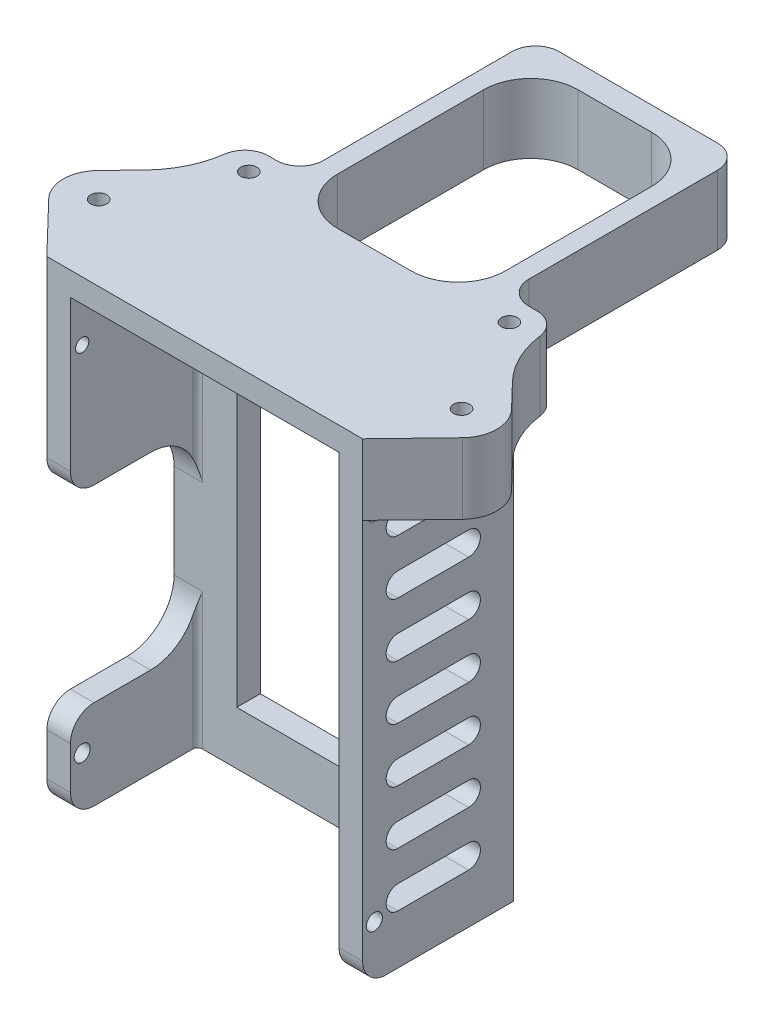
SolidWorks part; units mm, degrees
ref_plane "前视基准面" through (0, 0, 0) normal (0, 0, 1) x (1, 0, 0)
ref_plane "上视基准面" through (0, 0, 0) normal (0, 1, 0) x (1, 0, 0)
ref_plane "右视基准面" through (0, 0, 0) normal (1, 0, 0) x (0, 0, -1)
sketch "草图1" plane through (0, 0, 0) normal (0, 0, 1) x (1, 0, 0)
  line L1 (33.5, -59) -> (-33.5, -59)
  line L2 (33.5, -59) -> (33.5, 59)
  line L3 (33.5, 59) -> (-33.5, 59)
  line L4 (-33.5, -59) -> (-33.5, 59)
  line L5 (33.5, -59) -> (-33.5, 59) construction
  line L6 (33.5, 59) -> (-33.5, -59) construction
  point P0 (0, 0)
  dimension "D1" = 67
  dimension "D2" = 118
extrude "凸台-拉伸1" add sketch "草图1" along normal blind 32
shell "抽壳2" thickness 5
sketch "草图2" plane through (0, 0, 0) normal (0, 0, -1) x (-1, 0, 0)
  line L1 (20.2, -30.7) -> (-21.8, -30.7)
  line L2 (20.2, -30.7) -> (20.2, 44.3)
  line L3 (20.2, 44.3) -> (-21.8, 44.3)
  line L4 (-21.8, -30.7) -> (-21.8, 44.3)
  line L5 (-33.5, 59) -> (33.5, 59) construction
  line L6 (-33.5, -59) -> (-33.5, 59) construction
  point P0 (0, 0)
  dimension "D1" = 42
  dimension "D2" = 75
  dimension "D3" = 14.7
  dimension "D4" = 11.7
extrude "切除-拉伸1" cut sketch "草图2" against normal blind 5
sketch "草图3" plane through (0, 0, 0) normal (0, 0, -1) x (-1, 0, 0)
  line L0 (-21.8, -30.7) -> (20.2, -30.7) construction
  line L1 (-21.8, 44.3) -> (-21.8, -30.7) construction
  line L2 (20.2, 44.3) -> (-21.8, 44.3) construction
  line L3 (20.2, -30.7) -> (20.2, 44.3) construction
  line L4 (-21.8, -30.7) -> (20.2, -30.7)
  line L5 (-21.8, 44.3) -> (-21.8, -30.7)
  line L6 (20.2, 44.3) -> (-21.8, 44.3)
  line L7 (20.2, -30.7) -> (20.2, 44.3)
  line L8 (-25.8, -34.7) -> (24.2, -34.7)
  line L9 (24.2, -34.7) -> (24.2, 48.3)
  line L10 (24.2, 48.3) -> (-25.8, 48.3)
  line L11 (-25.8, 48.3) -> (-25.8, -34.7)
  dimension "D1" = 4
extrude "凸台-拉伸2" [suppressed] add sketch "草图3" along normal blind 24
sketch "草图4" plane through (-33.5, 0, 0) normal (-1, 0, 0) x (0, 0, 1)
  line L0 (32, 17) -> (1, 17)
  line L1 (32, 59) -> (32, -59) construction
  line L2 (1, -23) -> (1, 17)
  line L3 (1, -23) -> (32, -23)
  line L4 (32, -23) -> (32, 17)
  line L5 (32, 59) -> (0, 59) construction
  dimension "D1" = 42
  dimension "D2" = 40
  dimension "D3" = 31
extrude "切除-拉伸2" cut sketch "草图4" against normal blind 5
sketch "草图5" [suppressed] plane through (0, 0, -24) normal (0, 0, -1) x (-1, 0, 0)
  line L0 (0, 72.1156) -> (0, -68.0472) construction
  line L1 (-24.25, 45.3) -> (-14.25, 45.3)
  line L2 (-24.25, 45.3) -> (-24.25, 52.05)
  line L3 (14.25, 45.3) -> (14.25, 52.05)
  line L4 (-14.25, 45.3) -> (-14.25, 52.05)
  line L5 (-35.1719, 4.55) -> (42.7838, 4.55) construction
  line L6 (24.25, 45.3) -> (24.25, 52.05)
  line L7 (24.25, 45.3) -> (14.25, 45.3)
  line L8 (-14.25, -36.2) -> (-14.25, -42.95)
  line L9 (-24.25, -36.2) -> (-24.25, -42.95)
  line L10 (-24.25, -36.2) -> (-14.25, -36.2)
  line L11 (24.25, -36.2) -> (14.25, -36.2)
  line L12 (24.25, -36.2) -> (24.25, -42.95)
  line L13 (14.25, -36.2) -> (14.25, -42.95)
  arc A0 (-24.25, 52.05) -> (-14.25, 52.05) centre (-19.25, 52.05) cw
  circle A1 centre (-19.25, 52.05) radius 2.15
  circle A2 centre (19.25, 52.05) radius 2.15
  arc A3 (24.25, 52.05) -> (14.25, 52.05) centre (19.25, 52.05) ccw
  circle A4 centre (-19.25, -42.95) radius 2.15
  arc A5 (-24.25, -42.95) -> (-14.25, -42.95) centre (-19.25, -42.95) ccw
  arc A6 (24.25, -42.95) -> (14.25, -42.95) centre (19.25, -42.95) cw
  circle A7 centre (19.25, -42.95) radius 2.15
  dimension "D2" = 5
  dimension "D3" = 4.3
  dimension "D1" = 6.75
extrude "凸台-拉伸3" [suppressed] add sketch "草图5" against normal blind 8
ref_plane "基准面1" [suppressed] through (0, 0, -16) normal (0, 0, 1) x (1, 0, 0)
fillet "圆角2" [suppressed] radius 11
sketch "草图6" [suppressed] plane through (0, 0, -16) normal (0, 0, 1) x (1, 0, 0)
  line L0 (0, 85.8102) -> (0, -80.0918) construction
  line L1 (45.1986, 4.55) -> (-38.9545, 4.55) construction
  circle A0 centre (-19.25, -42.95) radius 3.75
  circle A1 centre (-19.25, 52.05) radius 3.75
  circle A2 centre (19.25, 52.05) radius 3.75
  circle A3 centre (19.25, -42.95) radius 3.75
  dimension "D1" = 7.5
extrude "切除-拉伸3" [suppressed] cut sketch "草图6" along normal blind 8
fillet "圆角3" [suppressed] radius 11
sketch "草图7" plane through (-33.5, 0, 0) normal (-1, 0, 0) x (0, 0, 1)
  line L0 (32, 59) -> (0, 59) construction
  line L1 (32, 59) -> (32, 17) construction
  line L3 (32, -23) -> (32, -59) construction
  circle A0 centre (29.5, 44) radius 1.4
  circle A2 centre (29.5, -31) radius 1.7
  dimension "D1" = 15
  dimension "D2" = 2.5
  dimension "D3" = 2.8
  dimension "D4" = 75
  dimension "D5" = 2.5
  dimension "D6" = 3.4
extrude "切除-拉伸4" cut sketch "草图7" against normal through all
sketch "草图9" plane through (-33.5, 0, 0) normal (-1, 0, 0) x (0, 0, 1)
  line L0 (0, 59) -> (0, -59) construction
  line L1 (32, -59) -> (0, -59)
  line L2 (32, -59) -> (32, -42)
  line L3 (32, -42) -> (0, -42)
  line L4 (0, -59) -> (0, -42)
  dimension "D1" = 17
extrude "切除-拉伸6" cut sketch "草图9" against normal through all
sketch "草图10" plane through (0, 0, 5) normal (0, 0, 1) x (1, 0, 0)
  line L0 (21.8, -30.7) -> (-20.2, -30.7) construction
  line L1 (-44.2, 59) -> (45.8, 59)
  line L2 (-44.2, 59) -> (-44.2, -42)
  line L3 (-44.2, -42) -> (45.8, -42)
  line L4 (45.8, 59) -> (45.8, -42)
  line L5 (21.8, 44.3) -> (21.8, -30.7) construction
  line L6 (-20.2, -30.7) -> (-20.2, 44.3) construction
  line L7 (-20.2, 44.3) -> (21.8, 44.3) construction
  line L8 (21.8, -30.7) -> (-20.2, -30.7)
  line L9 (21.8, 44.3) -> (21.8, -30.7)
  line L10 (-20.2, -30.7) -> (-20.2, 44.3)
  line L11 (-20.2, 44.3) -> (21.8, 44.3)
  line L12 (33.5, 59) -> (-33.5, 59) construction
  line L13 (28.5, -42) -> (-28.5, -42) construction
  line L14 (21.8, 6.8) -> (-20.2, 6.8) construction
  line L15 (0.8, 44.3) -> (0.8, -30.7) construction
  circle A0 centre (39.8, 39.3) radius 1.7
  circle A1 centre (39.8, -25.7) radius 1.7
  circle A2 centre (-38.2, -25.7) radius 1.7
  circle A3 centre (-38.2, 39.3) radius 1.7
  dimension "D2" = 6
  dimension "D3" = 3.4
  dimension "D1" = 90
  dimension "D4" = 65
extrude "凸台-拉伸4" add sketch "草图10" against normal blind 5
fillet "圆角5" radius 10 2 edges at (-31, -23, 5) (-31, 17, 5)
fillet "圆角6" radius 5 2 edges at (-31, -23, 32) (-31, 17, 32)
sketch "草图13" plane through (33.5, 0, 0) normal (1, 0, 0) x (0, 0, -1)
  line L0 (-17, 56) -> (-17, -42) construction
  line L2 (-32, -42) -> (-5, -42) construction
  line L3 (-24.5, 51.5) -> (-9.5, 51.5) construction
  line L4 (-24.5, 54) -> (-9.5, 54)
  line L5 (-24.5, 49) -> (-9.5, 49)
  line L6 (-32, -42) -> (-32, 59) construction
  line L7 (-32, 59) -> (-5, 59) construction
  line L8 (-24.5, 40) -> (-9.5, 40) construction
  line L9 (-24.5, 42.5) -> (-9.5, 42.5)
  line L10 (-24.5, 37.5) -> (-9.5, 37.5)
  line L11 (-24.5, 28.5) -> (-9.5, 28.5) construction
  line L12 (-24.5, 31) -> (-9.5, 31)
  line L13 (-24.5, 26) -> (-9.5, 26)
  line L14 (-24.5, 17) -> (-9.5, 17) construction
  line L15 (-24.5, 19.5) -> (-9.5, 19.5)
  line L16 (-24.5, 14.5) -> (-9.5, 14.5)
  line L17 (-24.5, 5.5) -> (-9.5, 5.5) construction
  line L18 (-24.5, 8) -> (-9.5, 8)
  line L19 (-24.5, 3) -> (-9.5, 3)
  line L20 (-24.5, -6) -> (-9.5, -6) construction
  line L21 (-24.5, -3.5) -> (-9.5, -3.5)
  line L22 (-24.5, -8.5) -> (-9.5, -8.5)
  line L23 (-24.5, -17.5) -> (-9.5, -17.5) construction
  line L24 (-24.5, -15) -> (-9.5, -15)
  line L25 (-24.5, -20) -> (-9.5, -20)
  line L26 (-24.5, -29) -> (-9.5, -29) construction
  line L27 (-24.5, -26.5) -> (-9.5, -26.5)
  line L28 (-24.5, -31.5) -> (-9.5, -31.5)
  arc A0 (-24.5, 54) -> (-24.5, 49) centre (-24.5, 51.5) ccw
  arc A1 (-9.5, 49) -> (-9.5, 54) centre (-9.5, 51.5) ccw
  arc A2 (-24.5, 42.5) -> (-24.5, 37.5) centre (-24.5, 40) ccw
  arc A3 (-9.5, 37.5) -> (-9.5, 42.5) centre (-9.5, 40) ccw
  arc A4 (-24.5, 31) -> (-24.5, 26) centre (-24.5, 28.5) ccw
  arc A5 (-9.5, 26) -> (-9.5, 31) centre (-9.5, 28.5) ccw
  arc A6 (-24.5, 19.5) -> (-24.5, 14.5) centre (-24.5, 17) ccw
  arc A7 (-9.5, 14.5) -> (-9.5, 19.5) centre (-9.5, 17) ccw
  arc A8 (-24.5, 8) -> (-24.5, 3) centre (-24.5, 5.5) ccw
  arc A9 (-9.5, 3) -> (-9.5, 8) centre (-9.5, 5.5) ccw
  arc A10 (-24.5, -3.5) -> (-24.5, -8.5) centre (-24.5, -6) ccw
  arc A11 (-9.5, -8.5) -> (-9.5, -3.5) centre (-9.5, -6) ccw
  arc A12 (-24.5, -15) -> (-24.5, -20) centre (-24.5, -17.5) ccw
  arc A13 (-9.5, -20) -> (-9.5, -15) centre (-9.5, -17.5) ccw
  arc A14 (-24.5, -26.5) -> (-24.5, -31.5) centre (-24.5, -29) ccw
  arc A15 (-9.5, -31.5) -> (-9.5, -26.5) centre (-9.5, -29) ccw
  point P8 (-17, 51.5)
  point P13 (0, 0)
  point P19 (-17, 40)
  point P26 (-17, 28.5)
  point P33 (-17, 17)
  point P40 (-17, 5.5)
  point P47 (-17, -6)
  point P54 (-17, -17.5)
  point P61 (-17, -29)
  dimension "D1" = 2.5
  dimension "D2" = 15
  dimension "D3" = 15
  dimension "D4" = 5
  dimension "D6" = 11.5
  dimension "D5" = 8
fillet "圆角10" radius 1 3 edges at (-28.5, -27.5, 5) (-28.5, 30.5, 5) (28.5, 6, 5)
extrude "切除-拉伸7" cut sketch "草图13" against normal blind 10 contours L10 A3 L9 A2 | L13 A5 L12 A4 | L22 A11 L21 A10 | L25 A13 L24 A12 | L15 A7 L16 A6 | L18 A9 L19 A8 | L27 A15 L28 A14
sketch "草图14" plane through (0, 0, 5) normal (0, 0, 1) x (1, 0, 0)
  line L1 (-33.5, 59) -> (-44.2, 59)
  line L2 (-33.5, 59) -> (-33.5, -42)
  line L3 (-33.5, -42) -> (-44.2, -42)
  line L4 (-44.2, 59) -> (-44.2, -42)
  line L5 (33.5, -42) -> (45.8, -42)
  line L6 (33.5, -42) -> (33.5, 59)
  line L7 (33.5, 59) -> (45.8, 59)
  line L8 (45.8, -42) -> (45.8, 59)
extrude "切除-拉伸8" cut sketch "草图14" against normal through all
fillet "圆角11" radius 5 2 edges at (31, -42, 32) (-31, -42, 32)
sketch "草图17" plane through (0, 59, 0) normal (0, 1, 0) x (1, 0, 0)
  line L0 (33.5, -16) -> (-33.5, -16) construction
  line L3 (0, 0) -> (0, -32) construction
  line L5 (33.5, -32) -> (33.5, 0) construction
  line L6 (33.5, -32) -> (43.9012, -21.2035)
  line L7 (33.5, 0) -> (43.9012, -10.7965)
  line L8 (33.5, -32) -> (33.5, 0)
  line L9 (-33.5, -32) -> (-33.5, 0)
  line L10 (-33.5, 0) -> (-43.9012, -10.7965)
  line L11 (-33.5, -32) -> (-43.9012, -21.2035)
  circle A0 centre (38.5, -16) radius 1.7
  arc A1 (43.9012, -21.2035) -> (43.9012, -10.7965) centre (38.5, -16) ccw
  arc A2 (-43.9012, -21.2035) -> (-43.9012, -10.7965) centre (-38.5, -16) cw
  circle A3 centre (-38.5, -16) radius 1.7
  point P13 (50.315, -20.4119)
  dimension "D1" = 3.4
  dimension "D3" = 15
  dimension "D2" = 5
extrude "凸台-拉伸8" add sketch "草图17" against normal blind 15 separate body
sketch "草图18" plane through (0, 44, 0) normal (0, -1, 0) x (1, 0, 0)
  circle A0 centre (-38.5, 16) radius 3
  circle A1 centre (38.5, 16) radius 3
  dimension "D1" = 6
  dimension "D2" = 6
extrude "切除-拉伸9" cut sketch "草图18" against normal blind 5
sketch "草图19" plane through (0, 0, 0) normal (0, 0, -1) x (-1, 0, 0)
  line L0 (20.2, 44.3) -> (-21.8, 44.3) construction
  line L1 (-33.5, 59) -> (33.5, 59)
  line L2 (-33.5, 59) -> (-33.5, 44.3)
  line L3 (-33.5, 44.3) -> (33.5, 44.3)
  line L4 (33.5, 59) -> (33.5, 44.3)
extrude "凸台-拉伸9" add sketch "草图19" along normal blind 60
sketch "草图21" plane through (0, 44.3, 0) normal (0, -1, 0) x (1, 0, 0)
  line L0 (33.5, 0) -> (21.8, 0) construction
  line L5 (33.5, -60) -> (21.8, -60)
  line L6 (33.5, -60) -> (33.5, -10)
  line L7 (33.5, -10) -> (21.8, -10)
  line L8 (21.8, -60) -> (21.8, -10)
  line L9 (21.8, 5) -> (21.8, 0) construction
  line L10 (0, 32) -> (0, -60) construction
  line L11 (28.5, 32) -> (-28.5, 32) construction
  line L12 (33.5, -60) -> (-33.5, -60) construction
  line L13 (-21.8, -60) -> (-21.8, -10)
  line L14 (-33.5, -10) -> (-21.8, -10)
  line L15 (-33.5, -60) -> (-33.5, -10)
  line L16 (-33.5, -60) -> (-21.8, -60)
  dimension "D1" = 10
extrude "切除-拉伸10" cut sketch "草图21" against normal blind 60
sketch "草图22" plane through (0, 44.3, 0) normal (0, -1, 0) x (1, 0, 0)
  line L0 (0, -60) -> (0, 32) construction
  line L1 (21.8, -60) -> (-21.8, -60) construction
  line L2 (28.5, 32) -> (-28.5, 32) construction
  line L3 (33.5, -10) -> (21.8, -10) construction
  line L4 (33.5, -10) -> (33.5, 0) construction
  circle A0 centre (27.65, -5) radius 1.7
  circle A1 centre (-27.65, -5) radius 1.7
  dimension "D1" = 3.4
  dimension "D2" = 5
  dimension "D3" = 5.85
extrude "切除-拉伸11" cut sketch "草图22" against normal blind 60
sketch "草图23" plane through (0, 44.3, 0) normal (0, -1, 0) x (1, 0, 0)
  circle A0 centre (27.65, -5) radius 3
  circle A1 centre (-27.65, -5) radius 3
  dimension "D1" = 6
  dimension "D2" = 6
extrude "切除-拉伸12" cut sketch "草图23" against normal blind 4
sketch "草图24" plane through (0, 44.3, 0) normal (0, -1, 0) x (1, 0, 0)
  line L0 (21.8, -60) -> (-21.8, -60) construction
  line L1 (17.8, -55) -> (-17.8, -55)
  line L2 (17.8, -55) -> (17.8, -4)
  line L3 (17.8, -4) -> (-17.8, -4)
  line L4 (-17.8, -55) -> (-17.8, -4)
  line L6 (-21.8, -60) -> (-21.8, -10) construction
  line L7 (21.8, -10) -> (21.8, -60) construction
  line L8 (33.5, 0) -> (-33.5, 0) construction
  dimension "D1" = 5
  dimension "D2" = 4
  dimension "D3" = 4
  dimension "D4" = 4
extrude "切除-拉伸13" cut sketch "草图24" against normal through all
fillet "圆角14" radius 5 6 edges at (33.5, 51.65, -10) (-33.5, 51.65, -10) (-21.8, 51.65, -10) (21.8, 51.65, -10) (21.8, 51.65, -60) (-21.8, 51.65, -60)
fillet "圆角15" radius 10 4 edges at (-17.8, 51.65, -55) (17.8, 51.65, -55) (17.8, 51.65, -4) (-17.8, 51.65, -4)
fillet "圆角16" radius 20 2 edges at (-33.5, 51.65, 0) (33.5, 51.65, 0)
